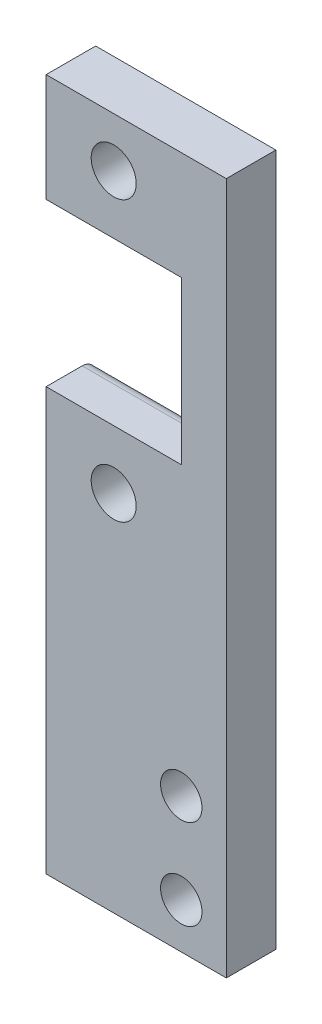
SolidWorks part; units mm, degrees
ref_plane "Front Plane" through (0, 0, 0) normal (0, 0, 1) x (1, 0, 0)
ref_plane "Top Plane" through (0, 0, 0) normal (0, 1, 0) x (1, 0, 0)
ref_plane "Right Plane" through (0, 0, 0) normal (1, 0, 0) x (0, 0, -1)
sketch "ProfileSketch3" plane through (0, 0, 0) normal (0, 0, 1) x (1, 0, 0)
  line L0 (0, 46.85) -> (15, 46.85)
  line L1 (0, 0) -> (20, 0)
  line L2 (0, 0) -> (0, 46.85)
  line L4 (20, 0) -> (20, 76.85)
  line L5 (15, 46.85) -> (15, 64.85)
  line L6 (15, 64.85) -> (0, 64.85)
  line L7 (0, 64.85) -> (0, 76.85)
  line L8 (0, 76.85) -> (20, 76.85)
  circle A0 centre (7.5, 40.35) radius 2.5
  circle A1 centre (7.5, 71.35) radius 2.5
  circle A2 centre (15, 15) radius 2.3
  circle A3 centre (15, 5) radius 2.3
  dimension "D8" = 5
  dimension "D12" = 4.6
  dimension "D6" = 20
  dimension "D1" = 46.85
  dimension "D4" = 12
  dimension "D5" = 5.5
  dimension "D7" = 6.5
  dimension "D3" = 31
  dimension "D10" = 18
  dimension "D11" = 6.5
  dimension "D2" = 7.5
  dimension "D9" = 5
  dimension "D13" = 5
  dimension "D14" = 10
  dimension "D15" = 5
extrude "ProfileBoss-Extrude1" add sketch "ProfileSketch3" along normal blind 5.5
fillet "Fillet1" radius 1.5 2 edges at (7.5, 46.85, 0) (7.5, 64.85, 0)
equation "\"SK8RodShaftSupportHeight\"= 42mm"
equation "\"SK8RodShaftSupportLength\"= 15mm"
equation "\"SK8MountHoleDiameter\"= 5mm"
equation "\"SK8RiserWidth\"= 6.75mm'Measured to meet Nema17 Mount Hole Center axis"
equation "\"SK8MountHoleFromSide\"= \"SK8RodShaftSupportLength\" / 2"
equation "\"SK8MountHoleFromEitherEnd\"= 5.5mm"
equation "\"MicroSwitchCutOutLength\"= 13.05mm"
equation "\"MicroSwitchHeight\"= 6.55mm"
equation "\"MicroSwitchMountingHoleOffsetFromSide\"= 3.35mm"
equation "\"MicroSwitchTerminalHeight\"= 3.5mm"
equation "\"MicroSwitchExtraMountingHeight\"= 2mm"
equation "\"MicroSwitchDepth\"= 2.8mm"
equation "\"MicroSwitchMountingHoleOffsetFromBottom\"= 7mm"
equation "\"M2HeatInsertHoleDiameter\"= 3mm + .1mm'Add .1mm for printing"
equation "\"M2HeatInsertHoleDepth\"= 3.1mm'Spec"
equation "\"D1@ProfileBoss-Extrude1\"=\"YAxisHolderThickness\""
equation "\"MicroSwitchCutOutHeight\"= \"MicroSwitchExtraMountingHeight\" + \"MicroSwitchTerminalHeight\" + \"MicroSwitchHeight\""
equation "\"EndStopCableWidth\"= 3.75mm"
equation "\"EndStopCableDepth\"= 1.75mm"
equation "\"D6@ProfileSketch3\"= \"YEndStopHolderLength\""
equation "\"D1@ProfileSketch3\"=\"MicroSwitchCutOutLength\" + \"SK8MountHoleFromEitherEnd\" * 1.6 +25mm"
equation "\"D4@ProfileSketch3\"=12mm"
equation "\"D5@ProfileSketch3\"=\"SK8MountHoleFromEitherEnd\""
equation "\"D8@ProfileSketch3\"=\"SK8MountHoleDiameter\""
equation "\"Nema17StepperMountSlotDistance\"=31"
equation "\"D3@ProfileSketch3\"=\"Nema17StepperMountSlotDistance\""
equation "\"D2@ProfileSketch3\"=\"SK8RodShaftSupportLength\"/2"
equation "\"M3HeatInsertDiameter\"=4.6"
equation "\"D12@ProfileSketch3\"=\"M3HeatInsertDiameter\""
equation "\"YAxisHolderThickness\"= \"M3HeatInsertHoleDepth\""
equation "\"YEndStopHolderLength\"= \"SK8RodShaftSupportLength\" + \"YEndStopBaseExtraLength\""
equation "\"YEndStopBaseExtraLength\"= 5mm"
equation "\"D9@ProfileSketch3\"=\"YEndStopBaseExtraLength\""
equation "\"M3HeatInsertHoleDepth\"= 5.5mm"
equation "\"D13@ProfileSketch3\"=\"YEndStopBaseExtraLength\""
